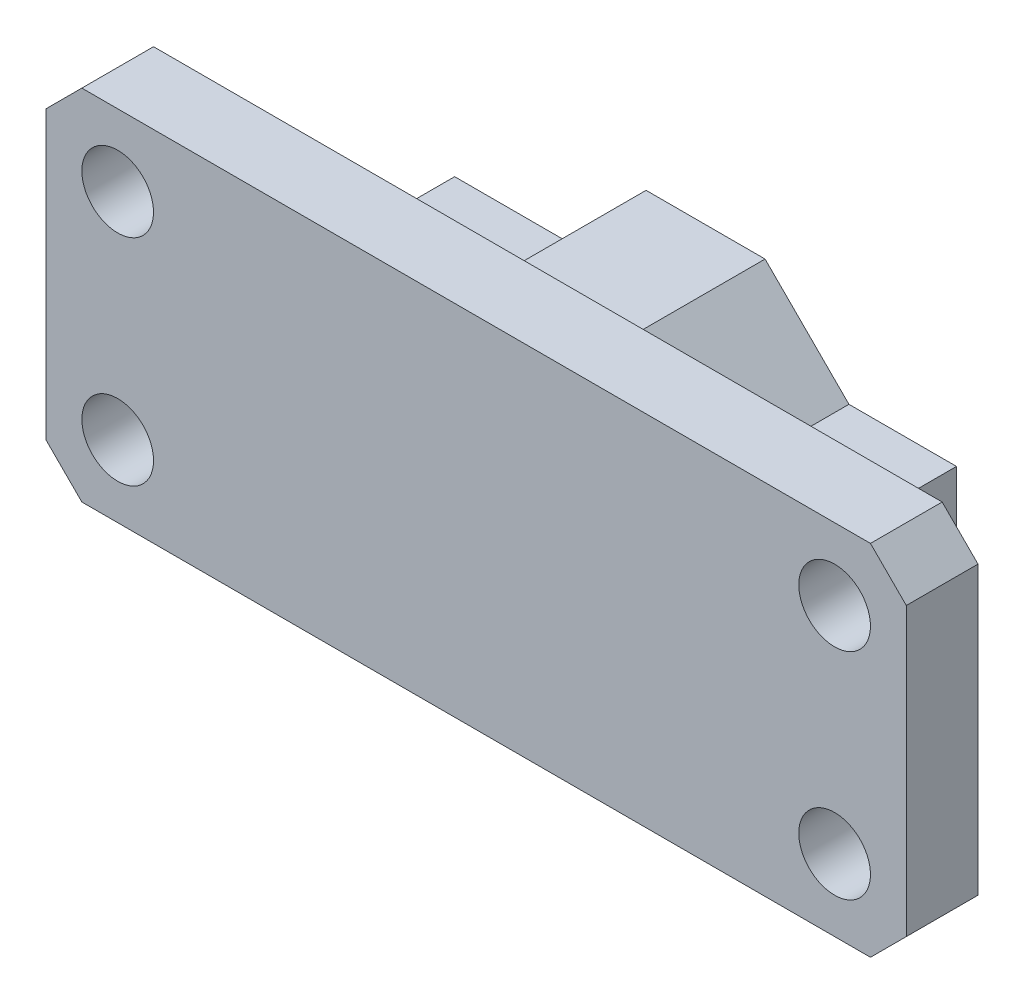
SolidWorks part; units mm, degrees
ref_plane "Спереди" through (0, 0, 0) normal (0, 0, 1) x (1, 0, 0)
ref_plane "Сверху" through (0, 0, 0) normal (0, 1, 0) x (1, 0, 0)
ref_plane "Справа" through (0, 0, 0) normal (1, 0, 0) x (0, 0, -1)
sketch "Эскиз доски" plane through (0, 0, 0) normal (0, 0, 1) x (1, 0, 0)
  line L0 (-60, 0) -> (60, 0) construction
  line L1 (-60, 25) -> (60, 25)
  line L2 (-60, 25) -> (-60, -25)
  line L3 (-60, -25) -> (60, -25)
  line L4 (60, 25) -> (60, -25)
  line L5 (-60, 25) -> (60, -25) construction
  line L6 (-60, -25) -> (60, 25) construction
  line L7 (0, 25) -> (0, -25) construction
  circle A0 centre (50, 15) radius 5
  circle A1 centre (-50, 15) radius 5
  circle A2 centre (-50, -15) radius 5
  circle A3 centre (50, -15) radius 5
  point P0 (0, 0)
  point P9 (51.0903, 10.1203)
  dimension "D4" = 10
  dimension "D1" = 50
  dimension "D2" = 10
  dimension "D5" = 120
  dimension "D6" = 10
extrude "Доска" add sketch "Эскиз доски" along normal blind 10 contours L1 L4 L3 L2
extrude "Отверстия в доске" cut sketch "Эскиз1<5>" against normal blind 10 from offset 10 contours A0 | A1 | A2 | A3
sketch "Эскиз1<5>" plane through (0, 0, 0) normal (0, 0, 1) x (1, 0, 0) same geometry as "Эскиз доски"
chamfer "Края доски" distance 5 angle 45 4 edges at (-60, 25, 5) (-60, -25, 5) (60, -25, 5) (60, 25, 5)
sketch "8угольник" plane through (0, 0, 0) normal (0, 0, -1) x (-1, 0, 0)
  line L0 (60, 0) -> (-60, 0) construction
  line L1 (0, 25) -> (0, -25) construction
  line L2 (-8.3, 20) -> (8.3, 20)
  line L5 (8.3, 20) -> (20, 8.3)
  line L6 (20, 8.3) -> (35, 8.3)
  line L7 (35, 8.3) -> (35, -8.3)
  line L8 (0, 25) -> (0, -25) construction
  line L9 (-8.3, 20) -> (-20, 8.3)
  line L10 (-20, 8.3) -> (-35, 8.3)
  line L11 (-35, 8.3) -> (-35, -8.3)
  line L12 (-20, -8.3) -> (-35, -8.3)
  line L13 (-8.3, -20) -> (-20, -8.3)
  line L14 (-8.3, -20) -> (8.3, -20)
  line L15 (8.3, -20) -> (20, -8.3)
  line L16 (20, -8.3) -> (35, -8.3)
  circle A0 centre (0, 0) radius 10
  point P20 (0, 20)
  point P24 (-35, 0)
  point P29 (35, 0)
  dimension "D6" = 20
  dimension "D1" = 8.3
  dimension "D2" = 15
  dimension "D3" = 11.7
  dimension "D4" = 8.3
  dimension "D5" = 11.7
extrude "8-угольник" add sketch "8угольник" along normal blind 32 from surface contours L9 L10 L11 L12 L13 L14 L15 L16 L7 L6 L5 L2 starting at face at (-55, 15, 10)
sketch "Эскиз3" plane through (0, 0, -22) normal (0, 0, -1) x (-1, 0, 0)
  line L0 (60, 0) -> (-60, 0) construction
  line L2 (-35, -8.3) -> (-35, 8.3) construction
  line L3 (-35, 8.3) -> (-20, 8.3) construction
  circle A0 centre (0, 0) radius 10
  point P3 (-26, 0)
  dimension "D1" = 20
  dimension "D2" = 26
  dimension "D3" = 9
  dimension "D4" = 8.3
extrude "Вырез-Вытянуть1" cut sketch "Эскиз3" against normal blind 22 contours A0
hole_wizard "Цековка для  болта с шестигранной головкой M51" positions "Эскиз4" profile "Эскиз6" counterbore size "M5" standard "ISO"
sketch "Эскиз4" plane through (0, 0, -22) normal (0, 0, -1) x (-1, 0, 0)
  point P0 (-26, 0)
sketch "Эскиз6" plane through (26, 0, -22) normal (1, 0, 0) x (0, 1, 0)
  line L0 (0, 0) -> (0, 25)
  line L1 (0, 25) -> (3, 25)
  line L2 (3, 25) -> (3, 5)
  line L3 (3, 5) -> (6, 5)
  line L4 (6, 5) -> (6, 0)
  line L5 (6, 0) -> (0, 0)
  line L10 (0, 25) -> (-3, 25) construction
  line L11 (0, -6.35) -> (0, 107.95) construction
  dimension "Диаметр отверстия" = 6
  dimension "Глубина отверстия" = 25
  dimension "Диаметр цековки" = 12
  dimension "Глубина цековки" = 5
  dimension "Угол заточки сверла" = 180
mirror "Зеркальное отражение1" about plane through (0, 0, 0) normal (1, 0, 0) of "Цековка для  болта с шестигранной головкой M51"
